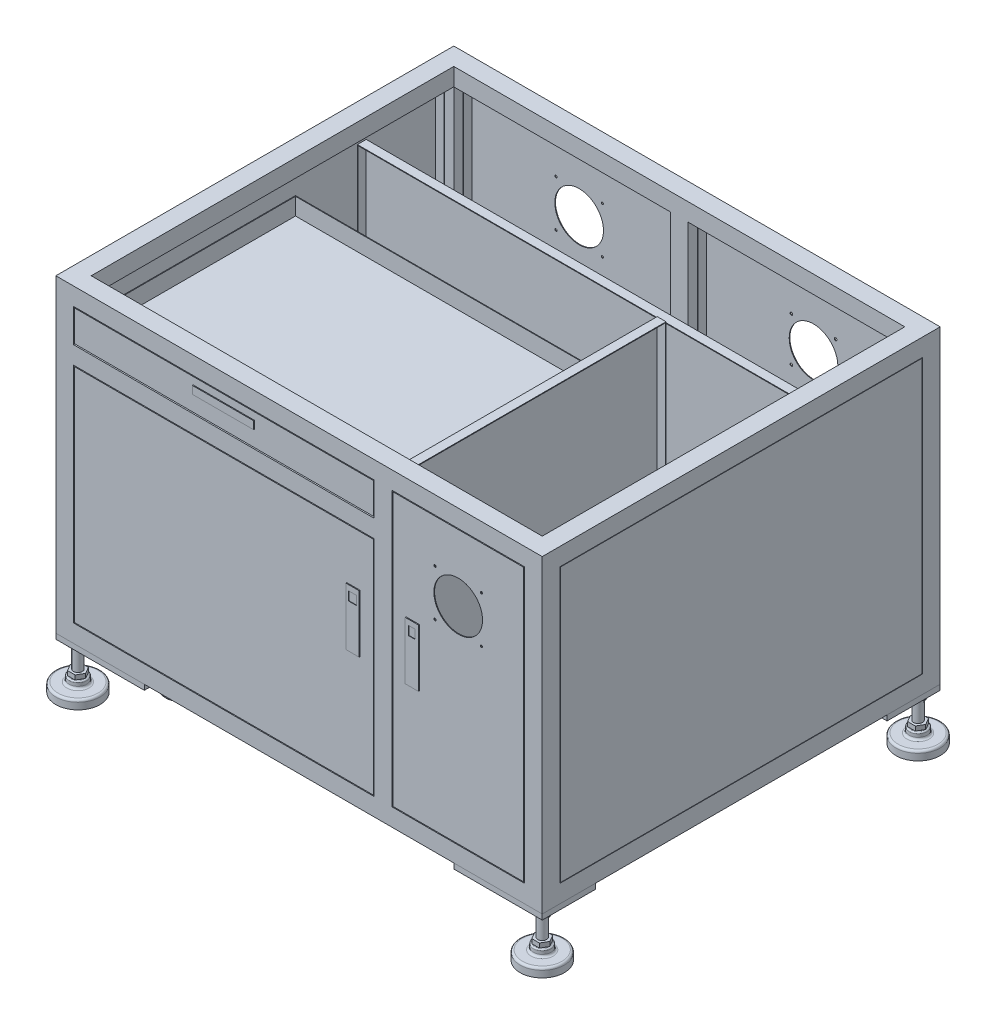
SolidWorks part; units mm, degrees
ref_plane "前视基准面" through (0, 0, 0) normal (0, 0, 1) x (1, 0, 0)
ref_plane "上视基准面" through (0, 0, 0) normal (0, 1, 0) x (1, 0, 0)
ref_plane "右视基准面" through (0, 0, 0) normal (1, 0, 0) x (0, 0, -1)
sketch "草图1" plane through (0, 0, 0) normal (0, 0, 1) x (1, 0, 0)
  line L1 (0, 0) -> (1100, 0)
  line L2 (0, 0) -> (0, 700)
  line L3 (0, 700) -> (1100, 700)
  line L4 (1100, 0) -> (1100, 700)
  dimension "D1" = 1100
  dimension "D2" = 700
extrude "凸台-拉伸1" add sketch "草图1" along normal blind 900
sketch "草图2" plane through (0, 0, 900) normal (0, 0, 1) x (1, 0, 0)
  line L10 (40, 660) -> (40, 40)
  line L11 (40, 40) -> (1060, 40)
  line L12 (1060, 40) -> (1060, 660)
  line L13 (1060, 660) -> (40, 660)
  line L14 (40, 660) -> (40, 40)
  line L15 (40, 40) -> (1060, 40)
  line L16 (1060, 40) -> (1060, 660)
  line L17 (1060, 660) -> (40, 660)
  dimension "D1" = 40
extrude "切除-拉伸1" cut sketch "草图2" against normal through all
sketch "草图3" plane through (0, 700, 0) normal (0, 1, 0) x (1, 0, 0)
  line L8 (1060, -40) -> (40, -40)
  line L9 (40, -40) -> (40, -860)
  line L10 (40, -860) -> (1060, -860)
  line L11 (1060, -860) -> (1060, -40)
  line L12 (1060, -40) -> (40, -40)
  line L13 (40, -40) -> (40, -860)
  line L14 (40, -860) -> (1060, -860)
  line L15 (1060, -860) -> (1060, -40)
  dimension "D1" = 40
extrude "切除-拉伸2" cut sketch "草图3" against normal through all
sketch "草图4" plane through (1100, 0, 0) normal (1, 0, 0) x (0, 0, -1)
  line L8 (-40, 40) -> (-40, 660)
  line L9 (-40, 660) -> (-860, 660)
  line L10 (-860, 660) -> (-860, 40)
  line L11 (-860, 40) -> (-40, 40)
  line L12 (-40, 40) -> (-40, 660)
  line L13 (-40, 660) -> (-860, 660)
  line L14 (-860, 660) -> (-860, 40)
  line L15 (-860, 40) -> (-40, 40)
  dimension "D1" = 40
extrude "切除-拉伸3" cut sketch "草图4" against normal through all
shell "抽壳1" thickness 2
sketch "草图5" plane through (0, 0, 0) normal (0, -1, 0) x (1, 0, 0)
  line L0 (0, 900) -> (1100, 900) construction
  line L1 (0, 900) -> (200, 900)
  line L2 (0, 900) -> (0, 780)
  line L3 (0, 780) -> (200, 780)
  line L4 (200, 900) -> (200, 780)
  line L5 (0, 900) -> (0, 0) construction
  line L7 (1100, 900) -> (900, 900)
  line L8 (1100, 900) -> (1100, 780)
  line L9 (1100, 780) -> (900, 780)
  line L10 (900, 900) -> (900, 780)
  line L11 (1100, 0) -> (900, 0)
  line L12 (1100, 0) -> (1100, 120)
  line L13 (1100, 120) -> (900, 120)
  line L14 (900, 0) -> (900, 120)
  line L15 (0, 0) -> (200, 0)
  line L16 (0, 0) -> (0, 120)
  line L17 (0, 120) -> (200, 120)
  line L18 (200, 0) -> (200, 120)
  dimension "D1" = 200
  dimension "D2" = 120
extrude "凸台-拉伸2" add sketch "草图5" along normal blind 12 separate body
sketch "草图6" plane through (0, 0, 0) normal (0, 1, 0) x (-1, 0, 0)
  line L4 (0, 900) -> (0, 0) construction
  line L5 (-1100, 0) -> (0, 0) construction
  line L6 (-1100, 900) -> (0, 900) construction
  line L7 (-1100, 900) -> (-1100, 0) construction
  circle A0 centre (-25, 25) radius 10
  circle A1 centre (-25, 875) radius 10
  circle A2 centre (-1075, 875) radius 10
  circle A3 centre (-1075, 25) radius 10
  dimension "D1" = 20
  dimension "D2" = 25
  dimension "D3" = 25
  dimension "D4" = 25
  dimension "D5" = 25
extrude "凸台-拉伸3" add sketch "草图6" along normal blind 50 and the other way blind 80
cosmetic thread "装饰螺纹线1" parameters "D2"=18
cosmetic thread "装饰螺纹线2" parameters "D2"=18
cosmetic thread "装饰螺纹线3" parameters "D2"=18
cosmetic thread "装饰螺纹线4" parameters "D2"=18
cosmetic thread "装饰螺纹线5" parameters "D2"=18
cosmetic thread "装饰螺纹线6" parameters "D2"=18
cosmetic thread "装饰螺纹线7" parameters "D2"=18
cosmetic thread "装饰螺纹线8" parameters "D2"=18
cosmetic thread "装饰螺纹线9" parameters "D2"=18
cosmetic thread "装饰螺纹线10" parameters "D2"=18
cosmetic thread "装饰螺纹线11" parameters "D2"=18
sketch "草图7" plane through (0, 0, 900) normal (0, 0, 1) x (1, 0, 0)
  line L0 (900, -12) -> (900, 0) construction
  line L1 (0, -12) -> (200, -12)
  line L2 (0, -12) -> (0, 0)
  line L3 (0, 0) -> (200, 0)
  line L4 (200, -12) -> (200, 0)
  line L5 (1100, -12) -> (900, -12)
  line L6 (1100, -12) -> (1100, 0)
  line L7 (1100, 0) -> (900, 0)
  line L8 (900, -12) -> (900, 0)
  line L9 (200, 0) -> (900, 0) construction
extrude "切除-拉伸4" cut sketch "草图7" against normal blind 0.1
sketch "草图8" plane through (1100, 0, 0) normal (1, 0, 0) x (0, 0, -1)
  line L1 (-899.9, -12) -> (-780, -12)
  line L2 (-899.9, -12) -> (-899.9, 0)
  line L3 (-899.9, 0) -> (-780, 0)
  line L4 (-780, -12) -> (-780, 0)
  line L5 (0, -12) -> (-120, -12)
  line L6 (0, -12) -> (0, 0)
  line L7 (0, 0) -> (-120, 0)
  line L8 (-120, -12) -> (-120, 0)
extrude "切除-拉伸5" cut sketch "草图8" against normal blind 0.1
sketch "草图9" plane through (0, 0, 0) normal (0, 0, -1) x (-1, 0, 0)
  line L1 (-900, -12) -> (-1100, -12)
  line L2 (-900, -12) -> (-900, 0)
  line L3 (-900, 0) -> (-1100, 0)
  line L4 (-1100, -12) -> (-1100, 0)
  line L5 (-200, 0) -> (0, 0)
  line L6 (-200, 0) -> (-200, -12)
  line L7 (-200, -12) -> (0, -12)
  line L8 (0, 0) -> (0, -12)
extrude "切除-拉伸6" cut sketch "草图9" against normal blind 0.1
sketch "草图10" plane through (0, 0, 0) normal (-1, 0, 0) x (0, 0, 1)
  line L1 (0.1, -12) -> (120, -12)
  line L2 (0.1, -12) -> (0.1, 0)
  line L3 (0.1, 0) -> (120, 0)
  line L4 (120, -12) -> (120, 0)
  line L5 (899.9, -12) -> (780, -12)
  line L6 (899.9, -12) -> (899.9, 0)
  line L7 (899.9, 0) -> (780, 0)
  line L8 (780, -12) -> (780, 0)
extrude "切除-拉伸7" cut sketch "草图10" against normal blind 0.1
sketch "草图11" plane through (0, -80, 0) normal (0, -1, 0) x (1, 0, 0)
  circle A0 centre (25, 875) radius 20
  circle A1 centre (25, 25) radius 20
  circle A2 centre (1075, 25) radius 20
  circle A3 centre (1075, 875) radius 20
  dimension "D1" = 40
extrude "凸台-拉伸4" add sketch "草图11" along normal blind 15
sketch "草图12" plane through (0, -95, 0) normal (0, -1, 0) x (1, 0, 0)
  circle A0 centre (25, 875) radius 50
  circle A1 centre (25, 25) radius 50
  circle A2 centre (1075, 25) radius 50
  circle A3 centre (1075, 875) radius 50
  dimension "D1" = 100
extrude "凸台-拉伸5" add sketch "草图12" along normal blind 20
fillet "圆角1" radius 3 4 edges at (25, -80, 855) (1075, -80, 855) (1075, -80, 5) (25, -80, 5)
fillet "圆角2" radius 5 4 edges at (1075, -95, 855) (1075, -95, 5) (25, -95, 5) (25, -95, 855)
fillet "圆角3" radius 5 4 edges at (1075, -95, -25) (25, -95, -25) (25, -95, 825) (1075, -95, 825)
sketch "草图15" plane through (0, -12, 0) normal (0, -1, 0) x (1, 0, 0)
  line L0 (0.1, 899.9) -> (200, 899.9) construction
  line L1 (33.6603, 860) -> (42.3205, 875)
  line L2 (42.3205, 875) -> (33.6603, 890)
  line L3 (33.6603, 890) -> (16.3397, 890)
  line L4 (16.3397, 890) -> (7.6795, 875)
  line L5 (7.6795, 875) -> (16.3397, 860)
  line L6 (16.3397, 860) -> (33.6603, 860)
  line L7 (1083.6603, 860) -> (1092.3205, 875)
  line L8 (1092.3205, 875) -> (1083.6603, 890)
  line L9 (1083.6603, 890) -> (1066.3397, 890)
  line L10 (1066.3397, 890) -> (1057.6795, 875)
  line L11 (1057.6795, 875) -> (1066.3397, 860)
  line L12 (1066.3397, 860) -> (1083.6603, 860)
  line L13 (1083.6603, 10) -> (1092.3205, 25)
  line L14 (1092.3205, 25) -> (1083.6603, 40)
  line L15 (1083.6603, 40) -> (1066.3397, 40)
  line L16 (1066.3397, 40) -> (1057.6795, 25)
  line L17 (1057.6795, 25) -> (1066.3397, 10)
  line L18 (1066.3397, 10) -> (1083.6603, 10)
  line L19 (33.6603, 10) -> (42.3205, 25)
  line L20 (42.3205, 25) -> (33.6603, 40)
  line L21 (33.6603, 40) -> (16.3397, 40)
  line L22 (16.3397, 40) -> (7.6795, 25)
  line L23 (7.6795, 25) -> (16.3397, 10)
  line L24 (16.3397, 10) -> (33.6603, 10)
  line L25 (200, 120) -> (0.1, 120) construction
  line L26 (1099.9, 120) -> (900, 120) construction
  line L27 (900, 899.9) -> (1099.9, 899.9) construction
  circle A0 centre (25, 875) radius 15 construction
  circle A1 centre (1075, 875) radius 15 construction
  circle A2 centre (1075, 25) radius 15 construction
  circle A3 centre (25, 25) radius 15 construction
  dimension "D1" = 30
extrude "凸台-拉伸7" add sketch "草图15" along normal blind 10
sketch "草图16" plane through (0, -80, 0) normal (0, 1, 0) x (1, 0, 0)
  line L0 (1092.3205, -25) -> (1083.6603, -40) construction
  line L1 (1066.3397, -860) -> (1057.6795, -875)
  line L2 (1057.6795, -875) -> (1066.3397, -890)
  line L3 (1066.3397, -890) -> (1083.6603, -890)
  line L4 (1083.6603, -890) -> (1092.3205, -875)
  line L5 (1092.3205, -875) -> (1083.6603, -860)
  line L6 (1083.6603, -860) -> (1066.3397, -860)
  line L7 (16.3397, -860) -> (7.6795, -875)
  line L8 (7.6795, -875) -> (16.3397, -890)
  line L9 (16.3397, -890) -> (33.6603, -890)
  line L10 (33.6603, -890) -> (42.3205, -875)
  line L11 (42.3205, -875) -> (33.6603, -860)
  line L12 (33.6603, -860) -> (16.3397, -860)
  line L13 (16.3397, -10) -> (7.6795, -25)
  line L14 (7.6795, -25) -> (16.3397, -40)
  line L15 (16.3397, -40) -> (33.6603, -40)
  line L16 (33.6603, -40) -> (42.3205, -25)
  line L17 (42.3205, -25) -> (33.6603, -10)
  line L18 (33.6603, -10) -> (16.3397, -10)
  line L19 (1083.6603, -10) -> (1066.3397, -10)
  line L20 (1066.3397, -10) -> (1057.6795, -25)
  line L21 (1057.6795, -25) -> (1066.3397, -40)
  line L22 (1066.3397, -40) -> (1083.6603, -40)
  line L23 (1083.6603, -40) -> (1092.3205, -25)
  line L24 (1092.3205, -25) -> (1083.6603, -10)
  line L25 (1092.3205, -875) -> (1083.6603, -890) construction
  line L26 (42.3205, -875) -> (33.6603, -890) construction
  line L27 (16.3397, -10) -> (33.6603, -10) construction
  circle A0 centre (1075, -875) radius 15 construction
  circle A1 centre (25, -875) radius 15 construction
  circle A2 centre (25, -25) radius 15 construction
  circle A3 centre (1075, -25) radius 15 construction
extrude "凸台-拉伸8" add sketch "草图16" along normal blind 10
sketch "草图17" plane through (0, -12, 0) normal (0, -1, 0) x (1, 0, 0)
  line L1 (900, 120) -> (1020, 120)
  line L2 (900, 120) -> (900, 50)
  line L3 (900, 50) -> (1020, 50)
  line L4 (1020, 120) -> (1020, 50)
  line L5 (900, 780) -> (1020, 780)
  line L6 (900, 780) -> (900, 850)
  line L7 (900, 850) -> (1020, 850)
  line L8 (1020, 780) -> (1020, 850)
  line L9 (200, 780) -> (80, 780)
  line L10 (200, 780) -> (200, 850)
  line L11 (200, 850) -> (80, 850)
  line L12 (80, 780) -> (80, 850)
  line L13 (200, 120) -> (80, 120)
  line L14 (200, 120) -> (200, 50)
  line L15 (200, 50) -> (80, 50)
  line L16 (80, 120) -> (80, 50)
  dimension "D1" = 120
  dimension "D2" = 70
extrude "凸台-拉伸9" add sketch "草图17" along normal blind 2 separate body
sketch "草图18" plane through (0, -14, 0) normal (0, -1, 0) x (1, 0, 0)
  line L0 (200, 85) -> (80, 85) construction
  line L1 (192.5, 80.5) -> (177.5, 80.5)
  line L2 (192.5, 80.5) -> (192.5, 89.5)
  line L3 (192.5, 89.5) -> (177.5, 89.5)
  line L4 (177.5, 80.5) -> (177.5, 89.5)
  line L5 (200, 50) -> (200, 120) construction
  line L6 (80, 120) -> (80, 50) construction
  line L7 (140, 50) -> (140, 120) construction
  line L8 (80, 50) -> (200, 50) construction
  line L9 (200, 120) -> (80, 120) construction
  line L10 (102.5, 80.5) -> (102.5, 89.5)
  line L11 (87.5, 89.5) -> (102.5, 89.5)
  line L12 (87.5, 80.5) -> (87.5, 89.5)
  line L13 (87.5, 80.5) -> (102.5, 80.5)
  line L14 (185, 89.5) -> (185, 80.5) construction
  line L15 (95, 89.5) -> (95, 80.5) construction
  dimension "D1" = 15
  dimension "D2" = 9
  dimension "D3" = 90
extrude "切除-拉伸8" cut sketch "草图18" against normal blind 2
fillet "圆角4" radius 2.5 8 edges at (192.5, -13, 80.5) (192.5, -13, 89.5) (177.5, -13, 89.5) (177.5, -13, 80.5) (102.5, -13, 80.5) (102.5, -13, 89.5) (87.5, -13, 89.5) (87.5, -13, 80.5)
ref_plane "基准面2" through (550, 0, 0) normal (1, 0, 0) x (0, 0, -1)
ref_plane "基准面3" through (0, 0, 450) normal (0, 0, 1) x (1, 0, 0)
sketch "草图27" plane through (0, -14, 0) normal (0, -1, 0) x (1, 0, 0)
  line L0 (140, 780) -> (140, 850) construction
  line L1 (97.5, 810.5) -> (112.5, 810.5)
  line L2 (97.5, 810.5) -> (97.5, 819.5)
  line L3 (97.5, 819.5) -> (112.5, 819.5)
  line L4 (112.5, 810.5) -> (112.5, 819.5)
  line L5 (80, 780) -> (200, 780) construction
  line L6 (200, 850) -> (80, 850) construction
  line L7 (80, 815) -> (200, 815) construction
  line L8 (80, 850) -> (80, 780) construction
  line L9 (200, 780) -> (200, 850) construction
  line L10 (167.5, 810.5) -> (167.5, 819.5)
  line L11 (182.5, 819.5) -> (167.5, 819.5)
  line L12 (182.5, 810.5) -> (182.5, 819.5)
  line L13 (182.5, 810.5) -> (167.5, 810.5)
  line L14 (175, 810.5) -> (175, 819.5) construction
  line L15 (105, 810.5) -> (105, 819.5) construction
  dimension "D1" = 15
  dimension "D2" = 9
  dimension "D3" = 70
extrude "切除-拉伸11" cut sketch "草图27" against normal blind 2
sketch "草图28" plane through (0, -14, 0) normal (0, -1, 0) x (1, 0, 0)
  line L0 (1020, 815) -> (900, 815) construction
  line L1 (987.5, 810.5) -> (1002.5, 810.5)
  line L2 (987.5, 810.5) -> (987.5, 819.5)
  line L3 (987.5, 819.5) -> (1002.5, 819.5)
  line L4 (1002.5, 810.5) -> (1002.5, 819.5)
  line L5 (1020, 780) -> (1020, 850) construction
  line L6 (900, 850) -> (900, 780) construction
  line L7 (960, 780) -> (960, 850) construction
  line L8 (900, 780) -> (1020, 780) construction
  line L9 (1020, 850) -> (900, 850) construction
  line L10 (917.5, 810.5) -> (917.5, 819.5)
  line L11 (932.5, 819.5) -> (917.5, 819.5)
  line L12 (932.5, 810.5) -> (932.5, 819.5)
  line L13 (932.5, 810.5) -> (917.5, 810.5)
  line L14 (995, 810.5) -> (995, 819.5) construction
  line L15 (925, 819.5) -> (925, 810.5) construction
  dimension "D1" = 9
  dimension "D2" = 15
  dimension "D3" = 70
extrude "切除-拉伸12" cut sketch "草图28" against normal blind 2
sketch "草图29" plane through (0, -14, 0) normal (0, -1, 0) x (1, 0, 0)
  line L0 (900, 85) -> (1020, 85) construction
  line L1 (917.5, 80.5) -> (932.5, 80.5)
  line L2 (917.5, 80.5) -> (917.5, 89.5)
  line L3 (917.5, 89.5) -> (932.5, 89.5)
  line L4 (932.5, 80.5) -> (932.5, 89.5)
  line L5 (900, 120) -> (900, 50) construction
  line L6 (960, 50) -> (960, 120) construction
  line L7 (900, 50) -> (1020, 50) construction
  line L8 (1020, 120) -> (900, 120) construction
  line L9 (1020, 50) -> (1020, 120) construction
  line L10 (987.5, 80.5) -> (987.5, 89.5)
  line L11 (1002.5, 89.5) -> (987.5, 89.5)
  line L12 (1002.5, 80.5) -> (1002.5, 89.5)
  line L13 (1002.5, 80.5) -> (987.5, 80.5)
  line L14 (995, 80.5) -> (995, 89.5) construction
  line L15 (925, 80.5) -> (925, 89.5) construction
  dimension "D1" = 15
  dimension "D2" = 9
  dimension "D3" = 70
extrude "切除-拉伸13" cut sketch "草图29" against normal blind 2
fillet "圆角7" radius 2.5 8 edges at (917.5, -13, 80.5) (917.5, -13, 89.5) (932.5, -13, 89.5) (932.5, -13, 80.5) (987.5, -13, 80.5) (987.5, -13, 89.5) (1002.5, -13, 89.5) (1002.5, -13, 80.5)
fillet "圆角8" radius 2.5 8 edges at (987.5, -13, 810.5) (987.5, -13, 819.5) (1002.5, -13, 819.5) (1002.5, -13, 810.5) (932.5, -13, 810.5) (932.5, -13, 819.5) (917.5, -13, 819.5) (917.5, -13, 810.5)
fillet "圆角9" radius 2.5 8 edges at (97.5, -13, 819.5) (112.5, -13, 819.5) (112.5, -13, 810.5) (97.5, -13, 810.5) (167.5, -13, 810.5) (167.5, -13, 819.5) (182.5, -13, 819.5) (182.5, -13, 810.5)
sketch "草图30" plane through (0, 0, 0) normal (-1, 0, 0) x (0, 0, 1)
  line L0 (860, 40) -> (40, 40) construction
  line L1 (41, 659) -> (859, 659)
  line L2 (41, 659) -> (41, 41)
  line L3 (41, 41) -> (859, 41)
  line L4 (859, 659) -> (859, 41)
  line L5 (860, 660) -> (860, 40) construction
  line L6 (40, 40) -> (40, 660) construction
  line L7 (40, 660) -> (860, 660) construction
  dimension "D1" = 1
  dimension "D2" = 1
  dimension "D3" = 1
  dimension "D4" = 1
extrude "凸台-拉伸15" add sketch "草图30" against normal blind 20 separate body
sketch "草图31" plane through (0, 40, 0) normal (0, 1, 0) x (1, 0, 0)
  line L0 (40, -40) -> (1060, -40) construction
  line L1 (41, -859) -> (1059, -859)
  line L2 (41, -859) -> (41, -41)
  line L3 (41, -41) -> (1059, -41)
  line L4 (1059, -859) -> (1059, -41)
  line L5 (40, -40) -> (40, -860) construction
  line L6 (1060, -860) -> (40, -860) construction
  line L7 (1060, -860) -> (1060, -40) construction
  dimension "D1" = 1
  dimension "D2" = 1
  dimension "D3" = 1
  dimension "D4" = 1
extrude "凸台-拉伸16" add sketch "草图31" against normal blind 20 separate body
sketch "草图32" plane through (1100, 0, 0) normal (1, 0, 0) x (0, 0, -1)
  line L0 (-860, 40) -> (-40, 40) construction
  line L1 (-859, 659) -> (-41, 659)
  line L2 (-859, 659) -> (-859, 41)
  line L3 (-859, 41) -> (-41, 41)
  line L4 (-41, 659) -> (-41, 41)
  line L5 (-40, 40) -> (-40, 660) construction
  line L6 (-860, 660) -> (-860, 40) construction
  line L7 (-40, 660) -> (-860, 660) construction
  dimension "D1" = 1
  dimension "D2" = 1
  dimension "D3" = 1
  dimension "D4" = 1
extrude "凸台-拉伸17" add sketch "草图32" against normal blind 20 separate body
shell "抽壳2" thickness 1.5 removed face at (1080, 350, 450)
shell "抽壳3" thickness 1.5 removed face at (20, 350, 450)
shell "抽壳4" thickness 1.5 removed face at (550, 20, 450)
sketch "草图33" plane through (0, 40, 0) normal (0, 1, 0) x (1, 0, 0)
  line L0 (40, 0) -> (1060, 0) construction
  line L1 (530, 0) -> (570, 0)
  line L2 (530, 0) -> (530, -40)
  line L3 (530, -40) -> (570, -40)
  line L4 (570, 0) -> (570, -40)
  line L5 (40, -40) -> (1060, -40) construction
  line L6 (550, 0) -> (550, -40) construction
  dimension "D1" = 40
extrude "凸台-拉伸18" add sketch "草图33" along normal up to surface (620 mm away) up to face at (550, 660, 20)
sketch "草图34" plane through (0, 40, 0) normal (0, 1, 0) x (1, 0, 0)
  line L0 (1060, -860) -> (40, -860) construction
  line L1 (530, -860) -> (570, -860)
  line L2 (530, -860) -> (530, -900)
  line L3 (530, -900) -> (570, -900)
  line L4 (570, -860) -> (570, -900)
  line L5 (40, -900) -> (1060, -900) construction
  line L6 (550, -900) -> (550, -860) construction
  dimension "D1" = 40
extrude "凸台-拉伸19" add sketch "草图34" along normal up to surface (620 mm away) up to face at (550, 660, 880)
sketch "草图35" plane through (0, 0, 0) normal (0, 0, -1) x (-1, 0, 0)
  line L0 (-40, 40) -> (-530, 40) construction
  line L1 (-529, 659) -> (-41, 659)
  line L2 (-529, 659) -> (-529, 41)
  line L3 (-529, 41) -> (-41, 41)
  line L4 (-41, 659) -> (-41, 41)
  line L5 (-530, 660) -> (-530, 40) construction
  line L6 (-40, 660) -> (-40, 40) construction
  line L7 (-530, 660) -> (-40, 660) construction
  dimension "D1" = 1
  dimension "D2" = 1
  dimension "D3" = 1
  dimension "D4" = 1
extrude "凸台-拉伸20" add sketch "草图35" against normal blind 20 separate body
shell "抽壳5" thickness 1.5 removed face at (285, 350, 20)
sketch "草图36" plane through (0, 0, 0) normal (0, 0, -1) x (-1, 0, 0)
  line L0 (-1060, 660) -> (-570, 660) construction
  line L1 (-1059, 659) -> (-571, 659)
  line L2 (-1059, 659) -> (-1059, 41)
  line L3 (-1059, 41) -> (-571, 41)
  line L4 (-571, 659) -> (-571, 41)
  line L5 (-1060, 40) -> (-1060, 660) construction
  line L6 (-570, 660) -> (-570, 40) construction
  line L7 (-570, 40) -> (-1060, 40) construction
  dimension "D1" = 1
  dimension "D2" = 1
  dimension "D3" = 1
  dimension "D4" = 1
extrude "凸台-拉伸21" add sketch "草图36" against normal blind 20 separate body
shell "抽壳6" thickness 1.5 removed face at (815, 350, 20)
sketch "草图37" plane through (0, 0, 900) normal (0, 0, 1) x (1, 0, 0)
  line L0 (40, 40) -> (530, 40) construction
  line L1 (41, 659) -> (529, 659)
  line L2 (41, 659) -> (41, 41)
  line L3 (41, 41) -> (529, 41)
  line L4 (529, 659) -> (529, 41)
  line L5 (40, 660) -> (40, 40) construction
  line L6 (530, 660) -> (530, 40) construction
  line L7 (530, 660) -> (40, 660) construction
  dimension "D1" = 1
  dimension "D2" = 1
  dimension "D3" = 1
  dimension "D4" = 1
extrude "凸台-拉伸22" add sketch "草图37" against normal blind 20 separate body
sketch "草图38" plane through (0, 0, 900) normal (0, 0, 1) x (1, 0, 0)
  line L0 (570, 40) -> (1060, 40) construction
  line L1 (571, 659) -> (1059, 659)
  line L2 (571, 659) -> (571, 41)
  line L3 (571, 41) -> (1059, 41)
  line L4 (1059, 659) -> (1059, 41)
  line L5 (570, 660) -> (570, 40) construction
  line L6 (1060, 40) -> (1060, 660) construction
  line L7 (1060, 660) -> (570, 660) construction
  dimension "D1" = 1
  dimension "D2" = 1
  dimension "D3" = 1
  dimension "D4" = 1
extrude "凸台-拉伸23" add sketch "草图38" against normal blind 20 separate body
shell "抽壳7" thickness 1.5 removed face at (815, 350, 880)
shell "抽壳8" thickness 1.5 removed face at (285, 350, 880)
sketch "草图43" plane through (0, 0, 0) normal (0, 0, -1) x (-1, 0, 0)
  line L0 (-815, 659) -> (-815, 215.6238) construction
  line L1 (-571, 659) -> (-1059, 659) construction
  line L2 (-815, 509) -> (-834.4915, 509) construction
  circle A0 centre (-815, 509) radius 55
  circle A1 centre (-865, 559) radius 3
  circle A2 centre (-865, 459) radius 3
  circle A3 centre (-765, 459) radius 3
  circle A4 centre (-765, 559) radius 3
  dimension "D1" = 110
  dimension "D2" = 150
  dimension "D3" = 6
  dimension "D4" = 100
  dimension "D5" = 100
extrude "切除-拉伸14" cut sketch "草图43" against normal through all contours A0 | A2 | A3 | A4 | A1 region at (815, 509, 0) region at (865, 559, 0) region at (865, 459, 0) region at (765, 459, 0) region at (765, 559, 0)
sketch "草图44" plane through (0, 0, 0) normal (0, 0, -1) x (-1, 0, 0)
  line L0 (-285, 660) -> (-285, 183.5766) construction
  line L1 (-530, 660) -> (-40, 660) construction
  line L2 (-41, 659) -> (-529, 659) construction
  line L3 (-285, 509) -> (-383.1689, 509) construction
  circle A0 centre (-285, 509) radius 55
  circle A1 centre (-337.5, 561.5) radius 2.5
  circle A2 centre (-337.5, 456.5) radius 2.5
  circle A3 centre (-232.5, 456.5) radius 2.5
  circle A4 centre (-232.5, 561.5) radius 2.5
  dimension "D1" = 110
  dimension "D2" = 150
  dimension "D3" = 5
  dimension "D4" = 105
  dimension "D5" = 105
extrude "切除-拉伸15" cut sketch "草图44" against normal through all contours A0 | A2 | A3 | A4 | A1 region at (285, 509, 0) region at (337.5, 561.5, 0) region at (337.5, 456.5, 0) region at (232.5, 456.5, 0) region at (232.5, 561.5, 0)
sketch "草图45" plane through (0, 0, 0) normal (0, 0, -1) x (-1, 0, 0)
  line L0 (-571, 41) -> (-571, 659) construction
  line L1 (-631, 429) -> (-611, 429)
  line L2 (-631, 429) -> (-631, 319)
  line L3 (-631, 319) -> (-611, 319)
  line L4 (-611, 429) -> (-611, 319)
  line L5 (-571, 659) -> (-1059, 659) construction
  line L6 (-550, 0) -> (-550, 184.0312) construction
  line L7 (0, 0) -> (-1100, 0) construction
  line L8 (-489, 429) -> (-489, 319)
  line L9 (-469, 319) -> (-489, 319)
  line L10 (-469, 429) -> (-469, 319)
  line L11 (-469, 429) -> (-489, 429)
  dimension "D1" = 20
  dimension "D2" = 110
  dimension "D3" = 40
  dimension "D4" = 230
extrude "凸台-拉伸26" add sketch "草图45" along normal blind 2 separate body
sketch "草图46" plane through (0, 0, -2) normal (0, 0, -1) x (-1, 0, 0)
  line L0 (-621, 429) -> (-621, 386.5451) construction
  line L1 (-626, 419) -> (-616, 419)
  line L2 (-626, 419) -> (-626, 409)
  line L3 (-626, 409) -> (-616, 409)
  line L4 (-616, 419) -> (-616, 409)
  line L5 (-611, 429) -> (-631, 429) construction
  dimension "D1" = 10
  dimension "D2" = 10
  dimension "D3" = 10
extrude "切除-拉伸16" cut sketch "草图46" against normal blind 1
sketch "草图47" plane through (0, 0, -2) normal (0, 0, -1) x (-1, 0, 0)
  line L0 (-479, 429) -> (-479, 379.6358) construction
  line L1 (-484, 419) -> (-474, 419)
  line L2 (-484, 419) -> (-484, 409)
  line L3 (-484, 409) -> (-474, 409)
  line L4 (-474, 419) -> (-474, 409)
  line L5 (-469, 429) -> (-489, 429) construction
  dimension "D1" = 10
  dimension "D2" = 10
  dimension "D3" = 10
extrude "切除-拉伸17" cut sketch "草图47" against normal blind 1
ref_plane "基准面4" through (0, 0, 260) normal (0, 0, -1) x (-1, 0, 0)
sketch "草图40" plane through (0, 0, 260) normal (0, 0, -1) x (-1, 0, 0)
  line L0 (-40, 660) -> (-40, 40) construction
  line L1 (-42, 658) -> (-1058, 658)
  line L2 (-42, 658) -> (-42, 42)
  line L3 (-42, 42) -> (-1058, 42)
  line L4 (-1058, 658) -> (-1058, 42)
  line L5 (-530, 660) -> (-40, 660) construction
  line L6 (-1060, 40) -> (-1060, 660) construction
  line L8 (-1060, 40) -> (-570, 40) construction
  dimension "D1" = 2
  dimension "D2" = 2
  dimension "D3" = 2
  dimension "D4" = 2
extrude "凸台-拉伸24" add sketch "草图40" along normal blind 20 separate body
shell "抽壳9" thickness 1.5 removed face at (550, 350, 260)
sketch "草图48" plane through (0, 0, 900) normal (0, 0, 1) x (1, 0, 0)
  line L0 (529, 41) -> (529, 659) construction
  line L1 (469, 429) -> (489, 429)
  line L2 (469, 429) -> (469, 319)
  line L3 (469, 319) -> (489, 319)
  line L4 (489, 429) -> (489, 319)
  line L5 (529, 659) -> (41, 659) construction
  line L6 (550, 0) -> (550, 200.2419) construction
  line L7 (0, 0) -> (1100, 0) construction
  line L8 (611, 429) -> (611, 319)
  line L9 (631, 319) -> (611, 319)
  line L10 (631, 429) -> (631, 319)
  line L11 (631, 429) -> (611, 429)
  dimension "D1" = 20
  dimension "D2" = 110
  dimension "D3" = 40
  dimension "D4" = 230
extrude "凸台-拉伸27" add sketch "草图48" along normal blind 2 separate body
sketch "草图49" plane through (0, 0, 902) normal (0, 0, 1) x (1, 0, 0)
  line L0 (479, 429) -> (479, 365.1712) construction
  line L1 (474, 419) -> (484, 419)
  line L2 (474, 419) -> (474, 409)
  line L3 (474, 409) -> (484, 409)
  line L4 (484, 419) -> (484, 409)
  line L5 (489, 429) -> (469, 429) construction
  dimension "D1" = 10
  dimension "D2" = 10
  dimension "D3" = 10
extrude "切除-拉伸18" cut sketch "草图49" against normal blind 1
sketch "草图50" plane through (0, 0, 902) normal (0, 0, 1) x (1, 0, 0)
  line L0 (621, 429) -> (621, 376.5881) construction
  line L1 (616, 419) -> (626, 419)
  line L2 (616, 419) -> (616, 409)
  line L3 (616, 409) -> (626, 409)
  line L4 (626, 419) -> (626, 409)
  line L5 (631, 429) -> (611, 429) construction
  dimension "D1" = 10
  dimension "D2" = 10
  dimension "D3" = 10
extrude "切除-拉伸19" cut sketch "草图50" against normal blind 1
sketch "草图51" plane through (0, -14, 0) normal (0, -1, 0) x (1, 0, 0)
  line L1 (900, 780) -> (970, 780)
  line L2 (900, 780) -> (900, 820)
  line L3 (900, 820) -> (970, 820)
  line L4 (970, 780) -> (970, 820)
  line L5 (550, 900) -> (550, 0) construction
  line L6 (0, 900) -> (1100, 900) construction
  line L7 (0, 0) -> (1100, 0) construction
  line L8 (0, 450) -> (1100, 450) construction
  line L9 (0, 900) -> (0, 0) construction
  line L10 (1100, 900) -> (1100, 0) construction
  line L11 (130, 780) -> (130, 820)
  line L12 (200, 820) -> (130, 820)
  line L13 (200, 780) -> (200, 820)
  line L14 (200, 780) -> (130, 780)
  line L15 (200, 120) -> (130, 120)
  line L16 (200, 120) -> (200, 80)
  line L17 (200, 80) -> (130, 80)
  line L18 (130, 120) -> (130, 80)
  line L19 (970, 120) -> (970, 80)
  line L20 (900, 80) -> (970, 80)
  line L21 (900, 120) -> (900, 80)
  line L22 (900, 120) -> (970, 120)
  dimension "D1" = 40
  dimension "D2" = 70
extrude "凸台-拉伸28" add sketch "草图51" along normal blind 60 separate body
sketch "草图52" plane through (130, 0, 0) normal (-1, 0, 0) x (0, 0, 1)
  line L0 (820, -74) -> (780, -74) construction
  line L1 (783, -74) -> (817, -74)
  line L2 (783, -74) -> (783, -19)
  line L3 (783, -19) -> (817, -19)
  line L4 (817, -74) -> (817, -19)
  line L5 (800, -74) -> (800, -20.6022) construction
  line L6 (820, -74) -> (820, -14) construction
  line L7 (820, -14) -> (780, -14) construction
  dimension "D1" = 3
  dimension "D2" = 5
extrude "切除-拉伸20" cut sketch "草图52" against normal up to surface (840 mm away) up to face at (970, -44, 800)
sketch "草图53" plane through (130, 0, 0) normal (-1, 0, 0) x (0, 0, 1)
  line L0 (120, -74) -> (80, -74) construction
  line L1 (83, -74) -> (117, -74)
  line L2 (83, -74) -> (83, -19)
  line L3 (83, -19) -> (117, -19)
  line L4 (117, -74) -> (117, -19)
  line L5 (100, -74) -> (100, -27.3194) construction
  line L6 (120, -74) -> (120, -14) construction
  line L7 (120, -14) -> (80, -14) construction
  dimension "D1" = 3
  dimension "D2" = 5
extrude "切除-拉伸21" cut sketch "草图53" against normal up to surface (840 mm away) up to face at (970, -44, 100)
sketch "草图54" plane through (0, 0, 820) normal (0, 0, 1) x (1, 0, 0)
  line L0 (165, -74) -> (165, -31.1753) construction
  line L1 (200, -74) -> (130, -74) construction
  line L2 (935, -74) -> (935, -21.6867) construction
  line L3 (970, -74) -> (900, -74) construction
  circle A0 centre (165, -54) radius 6
  circle A1 centre (935, -54) radius 6
  dimension "D1" = 12
  dimension "D2" = 20
  dimension "D3" = 12
  dimension "D4" = 20
extrude "切除-拉伸22" cut sketch "草图54" against normal up to surface (740 mm away) up to face at (935, -44, 80)
sketch "草图55" plane through (0, 0, 783) normal (0, 0, 1) x (1, 0, 0)
  circle A0 centre (935, -54) radius 34
  circle A1 centre (165, -54) radius 34
  dimension "D1" = 68
  dimension "D2" = 68
extrude "凸台-拉伸29" add sketch "草图55" along normal blind 33 separate body
sketch "草图56" plane through (0, 0, 117) normal (0, 0, -1) x (-1, 0, 0)
  circle A0 centre (-165, -54) radius 34
  circle A1 centre (-935, -54) radius 34
  dimension "D1" = 68
  dimension "D2" = 68
extrude "凸台-拉伸30" add sketch "草图56" along normal blind 33 separate body
fillet "圆角10" radius 2 2 edges at (901, -54, 117) (901, -54, 84)
fillet "圆角11" radius 2 2 edges at (131, -54, 117) (131, -54, 84)
fillet "圆角12" radius 2 2 edges at (199, -54, 816) (199, -54, 783)
fillet "圆角13" radius 2 2 edges at (969, -54, 816) (969, -54, 783)
fillet "圆角14" radius 30 4 edges at (900, -74, 818.5) (970, -74, 818.5) (970, -74, 781.5) (900, -74, 781.5)
fillet "圆角15" radius 30 4 edges at (200, -74, 818.5) (200, -74, 781.5) (130, -74, 818.5) (130, -74, 781.5)
fillet "圆角16" radius 30 4 edges at (200, -74, 118.5) (200, -74, 81.5) (130, -74, 118.5) (130, -74, 81.5)
fillet "圆角17" radius 30 4 edges at (900, -74, 118.5) (970, -74, 118.5) (970, -74, 81.5) (900, -74, 81.5)
sketch "草图57" plane through (0, 0, 240) normal (0, 0, -1) x (-1, 0, 0)
  line L0 (-550, 42) -> (-550, 658) construction
  line L1 (-92, 92) -> (-1008, 92)
  line L2 (-92, 92) -> (-92, 608)
  line L3 (-92, 608) -> (-1008, 608)
  line L4 (-1008, 92) -> (-1008, 608)
  line L5 (-1058, 42) -> (-42, 42) construction
  line L6 (-42, 350) -> (-550, 350) construction
  line L7 (-42, 42) -> (-42, 658) construction
  line L8 (-42, 658) -> (-1058, 658) construction
  dimension "D1" = 50
  dimension "D2" = 50
extrude "凸台-拉伸31" add sketch "草图57" along normal blind 20 separate body
sketch "草图58" plane through (0, 0, 900) normal (0, 0, 1) x (1, 0, 0)
  line L1 (40, 660) -> (1060, 660)
  line L2 (40, 660) -> (40, 40)
  line L3 (40, 40) -> (1060, 40)
  line L4 (1060, 660) -> (1060, 40)
extrude "切除-拉伸23" cut sketch "草图58" against normal blind 80 and the other way blind 20
sketch "草图59" plane through (0, 40, 0) normal (0, 1, 0) x (1, 0, 0)
  line L0 (1060, -860) -> (40, -860) construction
  line L1 (720, -860) -> (760, -860)
  line L2 (720, -860) -> (720, -900)
  line L3 (720, -900) -> (760, -900)
  line L4 (760, -860) -> (760, -900)
  line L5 (40, -900) -> (1060, -900) construction
  line L6 (1060, -860) -> (1060, -900) construction
  dimension "D1" = 300
  dimension "D2" = 40
extrude "凸台-拉伸32" add sketch "草图59" along normal up to surface (620 mm away) up to face at (285, 660, 20)
sketch "草图61" plane through (720, 0, 0) normal (-1, 0, 0) x (0, 0, 1)
  line L1 (860, 40) -> (260, 40)
  line L2 (860, 40) -> (860, 660)
  line L3 (860, 660) -> (260, 660)
  line L4 (260, 40) -> (260, 660)
  dimension "D1" = 600
extrude "凸台-拉伸34" add sketch "草图61" against normal blind 20 separate body
shell "抽壳10" thickness 1.5 removed face at (740, 350, 560)
sketch "草图62" plane through (0, 0, 900) normal (0, 0, 1) x (1, 0, 0)
  line L0 (40, 660) -> (40, 40) construction
  line L1 (42, 658) -> (718, 658)
  line L2 (42, 658) -> (42, 588)
  line L3 (42, 588) -> (718, 588)
  line L4 (718, 658) -> (718, 588)
  line L5 (720, 660) -> (40, 660) construction
  line L6 (720, 660) -> (720, 40) construction
  dimension "D1" = 2
  dimension "D2" = 2
  dimension "D3" = 2
  dimension "D4" = 70
extrude "凸台-拉伸35" add sketch "草图62" against normal blind 500 separate body
shell "抽壳11" thickness 1.5 removed face at (380, 658, 650)
sketch "草图64" plane through (0, 658, 0) normal (0, 1, 0) x (1, 0, 0)
  line L0 (42, -400) -> (42, -900) construction
  line L1 (42, -400) -> (718, -400)
  line L2 (42, -400) -> (42, -887.2897)
  line L3 (42, -887.2897) -> (718, -887.2897)
  line L4 (718, -400) -> (718, -887.2897)
  line L5 (718, -400) -> (718, -900) construction
  line L6 (718, -400) -> (42, -400) construction
extrude "切除-拉伸24" cut sketch "草图64" against normal blind 30
sketch "草图65" plane through (0, 0, 900) normal (0, 0, 1) x (1, 0, 0)
  line L0 (380, 658) -> (380, 588) construction
  line L1 (310.5264, 641.5548) -> (449.4736, 641.5548)
  line L2 (310.5264, 641.5548) -> (310.5264, 624.144)
  line L3 (310.5264, 624.144) -> (449.4736, 624.144)
  line L4 (449.4736, 641.5548) -> (449.4736, 624.144)
  line L5 (718, 658) -> (42, 658) construction
  line L6 (42, 588) -> (718, 588) construction
extrude "凸台-拉伸36" add sketch "草图65" along normal blind 2 separate body
sketch "草图66" plane through (40, 0, 0) normal (1, 0, 0) x (0, 0, -1)
  line L0 (-900, 660) -> (-900, 40) construction
  line L1 (-900, 585) -> (-860, 585)
  line L2 (-900, 585) -> (-900, 545)
  line L3 (-900, 545) -> (-860, 545)
  line L4 (-860, 585) -> (-860, 545)
  line L5 (-860, 40) -> (-860, 660) construction
  line L6 (-860, 660) -> (-900, 660) construction
  dimension "D1" = 75
  dimension "D2" = 40
extrude "凸台-拉伸37" add sketch "草图66" along normal up to surface (680 mm away) up to face at (720, 350, 880)
sketch "草图67" plane through (0, 0, 900) normal (0, 0, 1) x (1, 0, 0)
  line L0 (1060, 660) -> (760, 660) construction
  line L1 (762, 658) -> (1058, 658)
  line L2 (762, 658) -> (762, 42)
  line L3 (762, 42) -> (1058, 42)
  line L4 (1058, 658) -> (1058, 42)
  line L5 (760, 660) -> (760, 40) construction
  line L6 (1060, 40) -> (1060, 660) construction
  line L7 (760, 40) -> (1060, 40) construction
  dimension "D1" = 2
  dimension "D2" = 2
  dimension "D3" = 2
  dimension "D4" = 2
extrude "凸台-拉伸38" add sketch "草图67" against normal blind 20 separate body
sketch "草图68" plane through (0, 0, 900) normal (0, 0, 1) x (1, 0, 0)
  line L0 (762, 658) -> (762, 42) construction
  line L1 (792, 428) -> (822, 428)
  line L2 (792, 428) -> (792, 298)
  line L3 (792, 298) -> (822, 298)
  line L4 (822, 428) -> (822, 298)
  line L5 (1058, 658) -> (762, 658) construction
  dimension "D1" = 30
  dimension "D2" = 30
  dimension "D3" = 130
  dimension "D4" = 230
extrude "凸台-拉伸39" add sketch "草图68" along normal blind 2 separate body
sketch "草图69" plane through (0, 0, 902) normal (0, 0, 1) x (1, 0, 0)
  line L0 (807, 428) -> (807, 433.8107) construction
  line L1 (799.5, 416) -> (814.5, 416)
  line L2 (799.5, 416) -> (799.5, 396)
  line L3 (799.5, 396) -> (814.5, 396)
  line L4 (814.5, 416) -> (814.5, 396)
  line L5 (822, 428) -> (792, 428) construction
  dimension "D1" = 12
  dimension "D2" = 20
  dimension "D3" = 15
extrude "切除-拉伸25" cut sketch "草图69" against normal blind 1
sketch "草图70" plane through (0, 0, 900) normal (0, 0, 1) x (1, 0, 0)
  line L0 (40, 40) -> (720, 40) construction
  line L1 (42, 543) -> (718, 543)
  line L2 (42, 543) -> (42, 42)
  line L3 (42, 42) -> (718, 42)
  line L4 (718, 543) -> (718, 42)
  line L5 (40, 545) -> (40, 40) construction
  line L6 (720, 545) -> (40, 545) construction
  line L7 (720, 545) -> (720, 40) construction
  dimension "D1" = 2
  dimension "D2" = 2
  dimension "D3" = 2
  dimension "D4" = 2
extrude "凸台-拉伸40" add sketch "草图70" against normal blind 20 separate body
shell "抽壳12" thickness 1.5 removed face at (380, 292.5, 880)
sketch "草图71" plane through (0, 0, 900) normal (0, 0, 1) x (1, 0, 0)
  line L0 (718, 42) -> (718, 543) construction
  line L1 (688, 428) -> (658, 428)
  line L2 (688, 428) -> (688, 298)
  line L3 (688, 298) -> (658, 298)
  line L4 (658, 428) -> (658, 298)
  line L5 (718, 543) -> (42, 543) construction
  dimension "D1" = 30
  dimension "D2" = 30
  dimension "D3" = 130
  dimension "D4" = 115
extrude "凸台-拉伸41" add sketch "草图71" along normal blind 2 separate body
sketch "草图72" plane through (0, 0, 902) normal (0, 0, 1) x (1, 0, 0)
  line L0 (673, 428) -> (673, 394.4124) construction
  line L1 (664, 416) -> (682, 416)
  line L2 (664, 416) -> (664, 396)
  line L3 (664, 396) -> (682, 396)
  line L4 (682, 416) -> (682, 396)
  line L5 (688, 428) -> (658, 428) construction
  dimension "D1" = 18
  dimension "D2" = 20
  dimension "D3" = 12
extrude "切除-拉伸26" cut sketch "草图72" against normal blind 1
shell "抽壳13" thickness 1.5 removed face at (910, 350, 880)
sketch "草图77" plane through (0, 0, 900) normal (0, 0, 1) x (1, 0, 0)
  line L0 (910, 658) -> (910, 291.4767) construction
  line L1 (1058, 658) -> (762, 658) construction
  line L2 (910, 508) -> (793.3395, 508) construction
  circle A0 centre (910, 508) radius 55
  circle A1 centre (857.5, 560.5) radius 2.5
  circle A2 centre (857.5, 455.5) radius 2.5
  circle A3 centre (962.5, 455.5) radius 2.5
  circle A4 centre (962.5, 560.5) radius 2.5
  dimension "D1" = 110
  dimension "D2" = 105
  dimension "D3" = 105
  dimension "D4" = 5
  dimension "D5" = 150
extrude "切除-拉伸30" cut sketch "草图77" against normal blind 3
